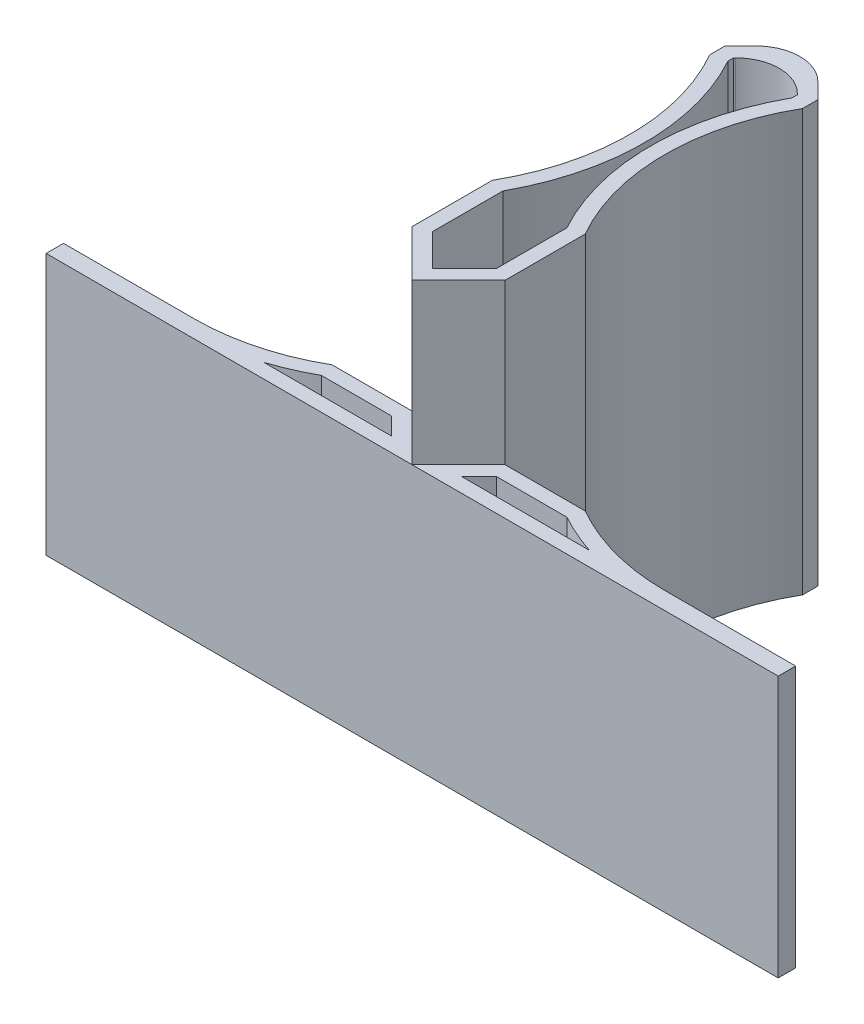
SolidWorks part; units mm, degrees
ref_plane "Front Plane" through (0, 0, 0) normal (0, 0, 1) x (1, 0, 0)
ref_plane "Top Plane" through (0, 0, 0) normal (0, 1, 0) x (1, 0, 0)
ref_plane "Right Plane" through (0, 0, 0) normal (1, 0, 0) x (0, 0, -1)
sketch "Sketch1" plane through (0, 0, 0) normal (0, 1, 0) x (1, 0, 0)
  line L0 (23.7595, 41.275) -> (41.275, 41.275) construction
  line L1 (-41.275, -41.275) -> (-23.7595, -41.275) construction
  line L2 (-41.275, -41.275) -> (-41.275, -23.7595) construction
  line L3 (-41.275, 41.275) -> (-23.7595, 41.275) construction
  line L4 (41.275, -41.275) -> (41.275, -23.7595) construction
  line L5 (-41.275, -41.275) -> (41.275, 41.275) construction
  line L6 (-41.275, 41.275) -> (41.275, -41.275) construction
  line L7 (41.275, 23.7595) -> (41.275, 41.275) construction
  line L8 (-41.275, 23.7595) -> (-41.275, 41.275) construction
  line L9 (23.7595, -41.275) -> (41.275, -41.275) construction
  line L10 (24.7569, 45.085) -> (45.085, 45.085) construction
  line L11 (45.085, 24.7569) -> (45.085, 45.085) construction
  line L12 (45.085, -45.085) -> (45.085, -24.7569) construction
  line L13 (24.7569, -45.085) -> (45.085, -45.085) construction
  line L14 (-45.085, -45.085) -> (-24.7569, -45.085) construction
  line L15 (-45.085, -45.085) -> (-45.085, -24.7569) construction
  line L16 (-45.085, 24.7569) -> (-45.085, 45.085) construction
  line L17 (-45.085, 45.085) -> (-24.7569, 45.085) construction
  line L19 (-51.435, -51.435) -> (51.435, -51.435) construction
  line L20 (-51.435, -51.435) -> (-51.435, 51.435) construction
  line L21 (-51.435, 51.435) -> (51.435, 51.435) construction
  line L22 (51.435, -51.435) -> (51.435, 51.435) construction
  line L23 (-51.435, -51.435) -> (51.435, 51.435) construction
  line L24 (-51.435, 51.435) -> (51.435, -51.435) construction
  arc A1 (-41.275, 23.7595) -> (-41.275, -23.7595) centre (0, 0) ccw construction
  arc A2 (23.7595, 41.275) -> (-23.7595, 41.275) centre (0, 0) ccw construction
  arc A3 (-23.7595, -41.275) -> (23.7595, -41.275) centre (0, 0) ccw construction
  arc A4 (41.275, -23.7595) -> (41.275, 23.7595) centre (0, 0) ccw construction
  arc A5 (45.085, -24.7569) -> (45.085, 24.7569) centre (0, 0) ccw construction
  arc A6 (-24.7569, -45.085) -> (24.7569, -45.085) centre (0, 0) ccw construction
  arc A7 (-45.085, 24.7569) -> (-45.085, -24.7569) centre (0, 0) ccw construction
  arc A8 (24.7569, 45.085) -> (-24.7569, 45.085) centre (0, 0) ccw construction
  point P0 (0, 0)
  dimension "D1" = 82.55
  dimension "D2" = 82.55
  dimension "D3" = 95.25
  dimension "D4" = 3.81
sketch "Sketch2" plane through (0, 0, 0) normal (0, 0, 1) x (1, 0, 0)
  line L0 (0, 48) -> (0, 0) construction
  line L1 (0, 0) -> (0, -9.15) construction
  line L2 (0, 48) -> (0, 82.925) construction
  dimension "Cage height" = 48
  dimension "Plate height" = 34.925
  dimension "D1" = 57.15
  dimension "D2" = 9.15
sketch "Sketch13" plane through (0, 0, 0) normal (0, 1, 0) x (1, 0, 0)
  line L0 (-51.435, -51.435) -> (51.435, -51.435) construction
  line L1 (-41.275, -41.275) -> (-23.7595, -41.275) construction
  line L2 (-41.275, -41.275) -> (-41.275, -23.7595) construction
  line L4 (-51.435, -51.435) -> (0, -51.435)
  line L5 (-41.275, -41.275) -> (-23.7595, -41.275)
  line L6 (-41.275, -41.275) -> (-41.275, -23.7595)
  line L9 (0, -47.625) -> (0, -51.435)
  line L10 (-51.435, 51.435) -> (51.435, -51.435) construction
  line L11 (-41.275, 23.7595) -> (-41.275, 41.275) construction
  line L12 (-51.435, -51.435) -> (-51.435, 51.435) construction
  line L13 (-51.435, 51.435) -> (-41.275, 41.275)
  line L14 (-41.275, 23.7595) -> (-41.275, 41.275)
  line L15 (-51.435, -51.435) -> (-51.435, 51.435)
  arc A0 (-23.7595, -41.275) -> (23.7595, -41.275) centre (0, 0) ccw construction
  arc A2 (-23.7595, -41.275) -> (0, -47.625) centre (0, 0) ccw
  arc A4 (-41.275, 23.7595) -> (-41.275, -23.7595) centre (0, 0) ccw construction
  arc A5 (-41.275, 23.7595) -> (-41.275, -23.7595) centre (0, 0) ccw
extrude "Boss-Extrude2" add sketch "Sketch13" along normal up to vertex (82.925 mm away) and the other way up to vertex (9.15 mm away) up to point (0, 82.925, 0) other way up to point (0, -9.15, 0)
sketch "Sketch15" plane through (0, 82.925, 0) normal (0, 1, 0) x (1, 0, 0)
  line L0 (0, 0) -> (-51.435, -51.435)
  line L1 (-51.435, -51.435) -> (0, -51.435)
  line L2 (0, -51.435) -> (0, 0)
  line L3 (-51.435, -51.435) -> (51.435, -51.435) construction
extrude "Cut-Extrude2" cut sketch "Sketch15" against normal up to vertex (34.925 mm away) up to point (0, 48, 0)
mirror "Mirror1" about plane through (-51.435, 82.925, 51.435) normal (1, 0, 0) of "Boss-Extrude2", "Cut-Extrude2"
sketch "Sketch16" plane through (0, -9.15, 0) normal (0, -1, 0) x (1, 0, 0)
  line L1 (-51.435, -51.435) -> (51.435, -51.435) construction
  circle A5 centre (-51.435, -13.335) radius 1.35
  dimension "D1" = 2.7
  dimension "D2" = 38.1
extrude "Cut-Extrude3" cut sketch "Sketch16" against normal blind 31.75
sketch "Sketch17" plane through (0, 82.925, 0) normal (0, 1, 0) x (1, 0, 0)
  line L0 (7.0944, 7.0944) -> (-7.0944, -7.0944)
  line L1 (7.0944, 7.0944) -> (-44.3406, 58.5294)
  line L2 (-7.0944, -7.0944) -> (-51.435, 37.2462)
  line L3 (-44.3406, 58.5294) -> (-51.435, 51.435)
  line L4 (-41.275, -41.275) -> (41.275, 41.275) construction
  line L5 (-61.595, 41.275) -> (-51.435, 51.435) construction
  line L6 (-51.435, -51.435) -> (-51.435, 51.435) construction
  line L7 (-51.435, 7.7321) -> (-51.435, 82.5591) construction
  line L8 (-95.7756, -7.0944) -> (-51.435, 37.2462)
  line L9 (-58.5294, 58.5294) -> (-51.435, 51.435)
  line L10 (-109.9644, 7.0944) -> (-58.5294, 58.5294)
  line L11 (-109.9644, 7.0944) -> (-95.7756, -7.0944)
  dimension "D1" = 20.066
extrude "Cut-Extrude4" cut sketch "Sketch17" against normal through all
sketch "Sketch18" plane through (0, 82.925, 0) normal (0, 1, 0) x (1, 0, 0)
  line L19 (-58.42, -24.5934) -> (-58.42, -39.9599)
  line L20 (-58.42, -39.9599) -> (-51.435, -46.9449)
  line L21 (-51.435, -46.9449) -> (-44.45, -39.9599)
  line L22 (-44.45, -39.9599) -> (-44.45, -24.5934)
  line L27 (-58.42, -24.5934) -> (-58.42, -39.9599)
  line L28 (-58.42, -39.9599) -> (-51.435, -46.9449)
  line L29 (-51.435, -46.9449) -> (-44.45, -39.9599)
  line L30 (-44.45, -39.9599) -> (-44.45, -24.5934)
  line L32 (-62.9101, -44.45) -> (-78.2766, -44.45)
  line L33 (-87.0077, -48.26) -> (-59.1001, -48.26)
  line L34 (-59.1001, -48.26) -> (-62.9101, -44.45)
  line L35 (-62.9101, -44.45) -> (-78.2766, -44.45)
  line L36 (-87.0077, -48.26) -> (-59.1001, -48.26)
  line L37 (-59.1001, -48.26) -> (-62.9101, -44.45)
  line L42 (-24.5934, -44.45) -> (-39.9599, -44.45)
  line L43 (-39.9599, -44.45) -> (-43.7699, -48.26)
  line L44 (-43.7699, -48.26) -> (-15.8623, -48.26)
  line L45 (-24.5934, -44.45) -> (-39.9599, -44.45)
  line L46 (-39.9599, -44.45) -> (-43.7699, -48.26)
  line L47 (-43.7699, -48.26) -> (-15.8623, -48.26)
  line L48 (-44.45, 25.7711) -> (-51.435, 32.7561)
  line L49 (-44.45, 25.7711) -> (-51.435, 32.7561)
  line L50 (-51.435, 32.7561) -> (-58.42, 25.7711)
  line L51 (-51.435, 32.7561) -> (-58.42, 25.7711)
  line L52 (-58.42, 25.7711) -> (-58.42, 24.5934)
  line L53 (-58.42, 25.7711) -> (-58.42, 24.5934)
  line L54 (-44.45, 24.5934) -> (-44.45, 25.7711)
  line L55 (-44.45, 24.5934) -> (-44.45, 25.7711)
  arc A5 (-87.0077, -48.26) -> (-78.2766, -44.45) centre (-102.87, 0) ccw
  arc A7 (-58.42, -24.5934) -> (-58.42, 24.5934) centre (-102.87, 0) ccw
  arc A8 (-44.45, 24.5934) -> (-44.45, -24.5934) centre (0, 0) ccw
  arc A10 (-58.42, -24.5934) -> (-58.42, 24.5934) centre (-102.87, 0) ccw
  arc A11 (-44.45, 24.5934) -> (-44.45, -24.5934) centre (0, 0) ccw
  arc A12 (-87.0077, -48.26) -> (-78.2766, -44.45) centre (-102.87, 0) ccw
  arc A14 (-24.5934, -44.45) -> (-15.8623, -48.26) centre (0, 0) ccw
  arc A15 (-24.5934, -44.45) -> (-15.8623, -48.26) centre (0, 0) ccw
  dimension "D1" = 3.175
  dimension "D2" = 3.175
  dimension "D3" = 3.175
extrude "Cut-Extrude5" cut sketch "Sketch18" against normal up to surface (60.325 mm away) contours A11 L55 L49 L51 L53 A10 L27 L28 L29 L30 region at (-51.435, 82.925, 12.1349) up to face at (-51.435, 22.6, -14.685)
sketch "Sketch22" plane through (0, 0, 0) normal (0, 1, 0) x (1, 0, 0)
  line L0 (-51.435, -51.435) -> (-51.435, 51.435) construction
  line L1 (-51.435, 51.435) -> (51.435, 51.435) construction
  circle A0 centre (-51.435, -12.065) radius 1.85
  dimension "D1" = 3.7
  dimension "D2" = 63.5
extrude "Cut-Extrude7" cut sketch "Sketch22" against normal through all both and the other way through all
sketch "Sketch20" plane through (0, 22.6, 0) normal (0, 1, 0) x (1, 0, 0)
  line L7 (-56.039, 19.685) -> (-46.831, 19.685)
  line L9 (-47.3448, -18.415) -> (-55.5252, -18.415)
  line L24 (-44.45, 24.5934) -> (-44.45, 25.7711)
  line L25 (-44.45, 25.7711) -> (-51.435, 32.7561)
  line L26 (-51.435, 32.7561) -> (-58.42, 25.7711)
  line L27 (-58.42, 25.7711) -> (-58.42, 24.5934)
  line L28 (-58.42, -24.5934) -> (-58.42, -39.9599)
  line L29 (-58.42, -39.9599) -> (-51.435, -46.9449)
  line L30 (-51.435, -46.9449) -> (-44.45, -39.9599)
  line L31 (-44.45, -39.9599) -> (-44.45, -24.5934)
  line L32 (-44.45, 24.5934) -> (-44.45, 25.7711)
  line L33 (-44.45, 25.7711) -> (-51.435, 32.7561)
  line L34 (-51.435, 32.7561) -> (-58.42, 25.7711)
  line L35 (-58.42, 25.7711) -> (-58.42, 24.5934)
  line L36 (-58.42, -24.5934) -> (-58.42, -39.9599)
  line L37 (-58.42, -39.9599) -> (-51.435, -46.9449)
  line L38 (-51.435, -46.9449) -> (-44.45, -39.9599)
  line L39 (-44.45, -39.9599) -> (-44.45, -24.5934)
  arc A0 (-58.42, -24.5934) -> (-58.42, 24.5934) centre (-102.87, 0) ccw construction
  arc A1 (-47.3448, -18.415) -> (-44.45, -24.5934) centre (0, 0) ccw
  arc A5 (-58.42, -24.5934) -> (-58.42, 24.5934) centre (-102.87, 0) ccw construction
  arc A9 (-44.45, 24.5934) -> (-44.45, -24.5934) centre (0, 0) ccw construction
  arc A11 (-44.45, 24.5934) -> (-44.45, -24.5934) centre (0, 0) ccw construction
  arc A13 (-58.42, -24.5934) -> (-58.42, 24.5934) centre (-102.87, 0) ccw
  arc A14 (-44.45, 24.5934) -> (-44.45, -24.5934) centre (0, 0) ccw
  arc A15 (-58.42, -24.5934) -> (-55.5252, -18.415) centre (-102.87, 0) ccw
  arc A16 (-44.45, 24.5934) -> (-46.831, 19.685) centre (0, 0) ccw
  arc A18 (-56.039, 19.685) -> (-58.42, 24.5934) centre (-102.87, 0) ccw
  circle A19 centre (-51.435, 13.335) radius 1.35 construction
  circle A20 centre (-51.435, -12.065) radius 1.85 construction
  dimension "D2" = 6.35
  dimension "D5" = 6.35
  dimension "D1" = 0
extrude "Cut-Extrude9" cut sketch "Sketch18<3>" against normal through all contours L36 L37 L35 A12 | L45 L46 L47 A15
sketch "Sketch18<3>" plane through (0, 82.925, 0) normal (0, 1, 0) x (1, 0, 0) same geometry as "Sketch18"
extrude "Cut-Extrude10" cut sketch "Sketch20" against normal through all
fillet "Fillet2" radius 9.525 2 edges at (-51.435, 36.8875, -37.2462) (-51.435, 36.8875, -32.7561)
sketch "Sketch23" plane through (0, 48, 0) normal (0, 1, 0) x (1, 0, 0)
  line L1 (0, -51.435) -> (28.575, -51.435)
  line L2 (0, -51.435) -> (0, -47.625)
  line L3 (0, -47.625) -> (28.575, -47.625)
  line L4 (28.575, -51.435) -> (28.575, -47.625)
  line L6 (-102.87, -51.435) -> (-131.445, -51.435)
  line L7 (-102.87, -51.435) -> (-102.87, -47.625)
  line L8 (-102.87, -47.625) -> (-131.445, -47.625)
  line L9 (-131.445, -51.435) -> (-131.445, -47.625)
  dimension "D1" = 28.575
extrude "Boss-Extrude3" add sketch "Sketch23" against normal up to surface (57.15 mm away) up to face at (-51.435, -9.15, -24.3743)
equation "\"tightTol\"= 0.005in"
equation "\"normTol\"= 0.01in"
equation "\"looseTol\"= 0.02in"
equation "\"Cage height@Sketch2\"=48mm"
equation "\"Plate height@Sketch2\"=1.375"
equation "\"D1@Sketch17\"=0.75in+2*\"looseTol\""
equation "\"D1@Sketch22\"=3.7mm"
equation "\"D1@Sketch16\"=2.7mm"
